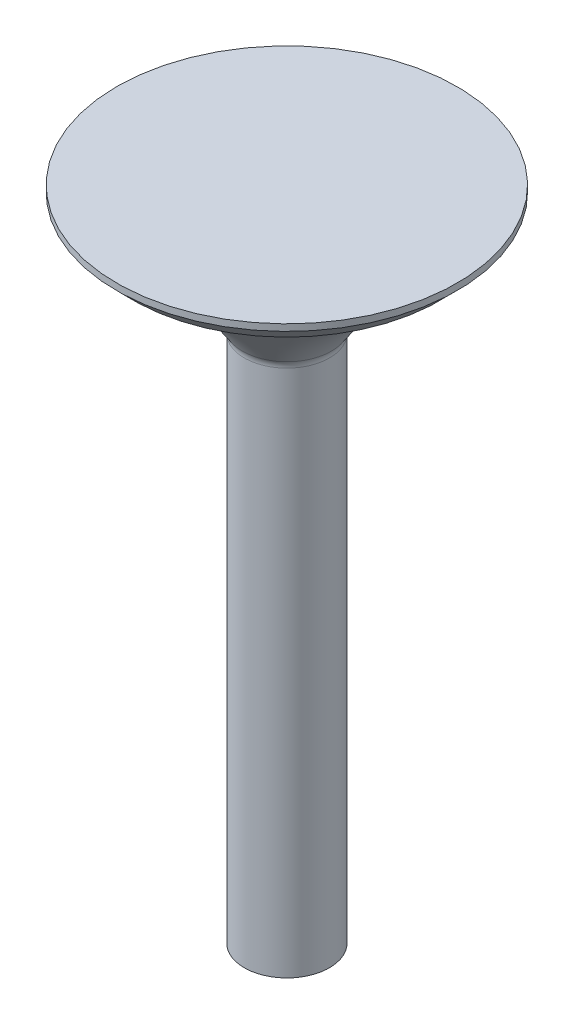
SolidWorks part; units mm, degrees
ref_plane "Front Plane" through (0, 0, 0) normal (0, 0, 1) x (1, 0, 0)
ref_plane "Top Plane" through (0, 0, 0) normal (0, 1, 0) x (1, 0, 0)
ref_plane "Right Plane" through (0, 0, 0) normal (1, 0, 0) x (0, 0, -1)
sketch "Sketch1" plane through (0, 0, 0) normal (0, 0, 1) x (1, 0, 0)
  line L0 (0, 224.083) -> (0, 124.083) construction
  line L1 (0, 224.083) -> (-25.92, 224.083)
  line L2 (-25.92, 224.083) -> (-25.92, 223.083)
  line L3 (-25.92, 223.083) -> (-23.328, 220.491)
  line L5 (-6.48, 205.053) -> (-6.48, 124.083)
  line L6 (-6.48, 124.083) -> (0, 124.083)
  line L7 (0, 224.083) -> (0, 124.083)
  arc A2 (-23.328, 220.491) -> (-6.48, 205.053) centre (-40.8014, 184.5093) cw
  dimension "D8" = 40
  dimension "D1" = 25.92
  dimension "D3" = 23.328
  dimension "D2" = 45
  dimension "D4" = 6.48
  dimension "D5" = 18.03
  dimension "D6" = 1
  dimension "D7" = 100
revolve "Revolve1" add sketch "Sketch1" angle 360 about L0
fillet "Fillet4" radius 2 1 edges at (-6.48, 205.053, 0)
equation "\"Valve Diameter\"= 51.84mm"
equation "\"Seat Angle Beta\"= 45deg"
equation "\"Seat Diameter\"= 46.656mm"
equation "\"Stem Diameter\"= 12.96mm"
equation "\"Max Lift\"= 18.03mm"
equation "\"Seat Width\"= 2.592mm"
equation "\"D1@Sketch1\"=\"Valve Diameter\"/2"
equation "\"D2@Sketch1\"=\"Seat Angle Beta\""
equation "\"D3@Sketch1\"=\"Seat Diameter\"/2"
equation "\"D5@Sketch1\"=\"Max Lift\""
equation "\"Head Thickness\"= 1mm"
equation "\"D6@Sketch1\"=\"Head Thickness\""
equation "\"Overall Length\" = 100mm"
equation "\"D7@Sketch1\"=\"Overall Length\""
